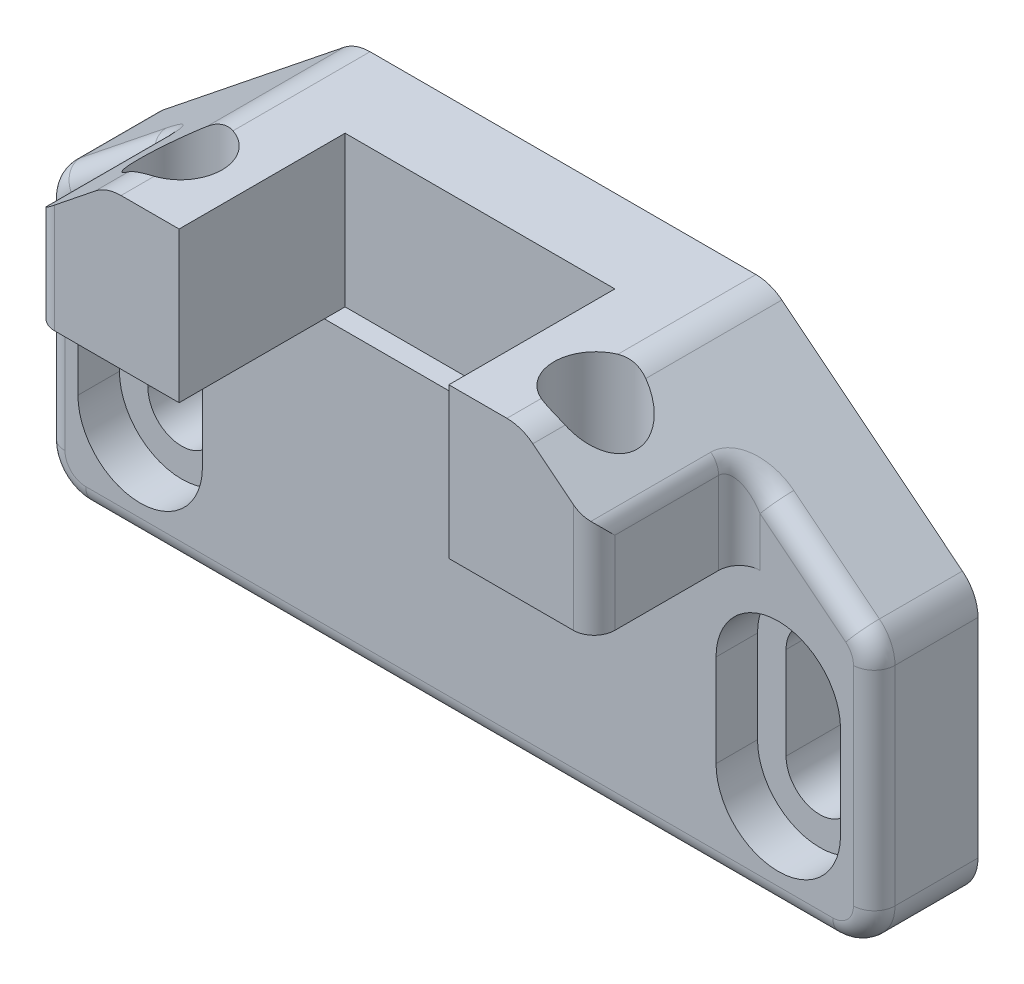
SolidWorks part; units mm, degrees
ref_plane "Front Plane" through (0, 0, 0) normal (0, 0, 1) x (1, 0, 0)
ref_plane "Top Plane" through (0, 0, 0) normal (0, 1, 0) x (1, 0, 0)
ref_plane "Right Plane" through (0, 0, 0) normal (1, 0, 0) x (0, 0, -1)
sketch "Sketch1" plane through (0, 0, 0) normal (0, 0, 1) x (1, 0, 0)
  line L0 (0, 0) -> (18, 0)
  line L1 (20, 2) -> (20, 12.0388)
  line L2 (19.2494, 13.6005) -> (10.5478, 20.5617)
  line L3 (9.2984, 21) -> (-9.2984, 21)
  line L4 (-10.5478, 20.5617) -> (-19.2494, 13.6005)
  line L5 (-20, 12.0388) -> (-20, 2)
  line L6 (-18, 0) -> (0, 0)
  line L7 (0, 21) -> (0, 0) construction
  line L8 (-15.375, 9.075) -> (-15.375, 4.625) construction
  line L9 (-13.75, 9.075) -> (-13.75, 4.625)
  line L10 (-17, 9.075) -> (-17, 4.625)
  line L11 (15.375, 9.075) -> (15.375, 4.625) construction
  line L12 (17, 9.075) -> (17, 4.625)
  line L13 (13.75, 9.075) -> (13.75, 4.625)
  arc A0 (-13.75, 9.075) -> (-17, 9.075) centre (-15.375, 9.075) ccw
  arc A1 (-17, 4.625) -> (-13.75, 4.625) centre (-15.375, 4.625) ccw
  arc A2 (17, 9.075) -> (13.75, 9.075) centre (15.375, 9.075) ccw
  arc A3 (13.75, 4.625) -> (17, 4.625) centre (15.375, 4.625) ccw
  arc A4 (-9.2984, 21) -> (-10.5478, 20.5617) centre (-9.2984, 19) ccw
  arc A5 (9.2984, 21) -> (10.5478, 20.5617) centre (9.2984, 19) cw
  arc A6 (-20, 12.0388) -> (-19.2494, 13.6005) centre (-18, 12.0388) cw
  arc A7 (19.2494, 13.6005) -> (20, 12.0388) centre (18, 12.0388) cw
  arc A8 (20, 2) -> (18, 0) centre (18, 2) cw
  arc A9 (-20, 2) -> (-18, 0) centre (-18, 2) ccw
  point P10 (-15.375, 6.85)
  point P16 (15.375, 6.85)
  point P23 (15.375, 3)
  point P24 (-15.375, 3)
  point P25 (-15.375, 10.7)
  point P28 (-10, 21)
  point P31 (10, 21)
  point P34 (-20, 13)
  point P37 (20, 13)
  point P40 (20, 0)
  point P43 (-20, 0)
  dimension "D14" = 2
  dimension "D1" = 20
  dimension "D2" = 20
  dimension "D3" = 21
  dimension "D4" = 13
  dimension "D5" = 13
  dimension "D6" = 20
  dimension "D7" = 3.25
  dimension "D8" = 3.25
  dimension "D9" = 3
  dimension "D10" = 3
  dimension "D11" = 7.7
  dimension "D12" = 3
  dimension "D13" = 3
extrude "Boss-Extrude1" add sketch "Sketch1" along normal blind 5
sketch "Sketch2" plane through (0, 0, 5) normal (0, 0, 1) x (1, 0, 0)
  line L0 (-15.375, 4.625) -> (-15.375, 9.075) construction
  line L1 (-18.375, 4.625) -> (-18.375, 9.075)
  line L2 (-12.375, 4.625) -> (-12.375, 9.075)
  line L3 (15.375, 4.625) -> (15.375, 9.075) construction
  line L4 (12.375, 4.625) -> (12.375, 9.075)
  line L5 (18.375, 4.625) -> (18.375, 9.075)
  arc A0 (-18.375, 4.625) -> (-12.375, 4.625) centre (-15.375, 4.625) ccw
  arc A1 (-12.375, 9.075) -> (-18.375, 9.075) centre (-15.375, 9.075) ccw
  arc A2 (12.375, 4.625) -> (18.375, 4.625) centre (15.375, 4.625) ccw
  arc A3 (18.375, 9.075) -> (12.375, 9.075) centre (15.375, 9.075) ccw
  point P4 (-15.375, 6.85)
  point P9 (15.375, 6.85)
  dimension "D1" = 6
  dimension "D2" = 6
extrude "Cut-Extrude1" cut sketch "Sketch2" against normal blind 2
sketch "Sketch3" plane through (0, 0, 5) normal (0, 0, 1) x (1, 0, 0)
  line L0 (-13.5, 13.75) -> (13.5, 13.75)
  line L1 (13.5, 13.75) -> (13.5, 21)
  line L2 (13.5, 21) -> (-13.5, 21)
  line L3 (-13.5, 21) -> (-13.5, 13.75)
  line L4 (0, 21) -> (0, 0) construction
  line L5 (9.2984, 21) -> (-9.2984, 21) construction
  point P6 (0, 0)
  dimension "D1" = 27
  dimension "D2" = 7.25
extrude "Boss-Extrude2" add sketch "Sketch3" along normal blind 7
sketch "Sketch4" plane through (0, 0, 12) normal (0, 0, 1) x (1, 0, 0)
  line L0 (13.5, 18.2) -> (10.5478, 20.5617)
  line L1 (-13.5, 18.2) -> (-10.5478, 20.5617)
  line L2 (13.5, 18.2) -> (13.5, 21)
  line L3 (13.5, 21) -> (9.2984, 21)
  line L4 (13.5, 21) -> (-13.5, 21) construction
  line L5 (-13.5, 18.2) -> (-13.5, 21)
  line L6 (-13.5, 21) -> (-9.2984, 21)
  line L7 (-6.5, 21) -> (-6.5, 13.75)
  line L8 (-13.5, 13.75) -> (13.5, 13.75) construction
  line L9 (-6.5, 13.75) -> (6.5, 13.75)
  line L10 (-13.5, 13.75) -> (13.5, 13.75) construction
  line L11 (6.5, 13.75) -> (6.5, 21)
  line L12 (6.5, 21) -> (-6.5, 21)
  line L13 (0, 21) -> (0, 0) construction
  arc A0 (-10.5478, 20.5617) -> (-9.2984, 21) centre (-9.2984, 19) cw
  arc A1 (-9.2984, 21) -> (-10.5478, 20.5617) centre (-9.2984, 19) ccw construction
  arc A2 (10.5478, 20.5617) -> (9.2984, 21) centre (9.2984, 19) ccw
  point P32 (0, 0)
  dimension "D1" = 13
extrude "Cut-Extrude2" cut sketch "Sketch4" against normal blind 8
sketch "Sketch5" plane through (0, 13.75, 0) normal (0, -1, 0) x (1, 0, 0)
  line L2 (-13.5, 12) -> (-6.5, 12) construction
  line L3 (6.5, 12) -> (13.5, 12) construction
  circle A0 centre (-9.9308, 8.5) radius 2
  circle A1 centre (10.0692, 8.5) radius 2
  point P7 (-9.6925, 9.1873)
  dimension "D1" = 4
  dimension "D3" = 3.5
  dimension "D4" = 3.5
  dimension "D2" = 20
extrude "Cut-Extrude3" cut sketch "Sketch5" against normal through all
fillet "Fillet1" radius 1 15 edges at (13.5, 18.2, 8.5) (16.3747, 15.9002, 5) (19.8026, 12.9051, 5) (20, 7.0194, 5) (19.4142, 0.5858, 5) (0, 0, 5) (-19.4142, 0.5858, 5) (-20, 7.0194, 5) (-19.8026, 12.9051, 5) (-16.3747, 15.9002, 5) (-13.5, 18.2, 8.5) (-13.5, 15.975, 5) (13.5, 15.975, 5) (13.5, 15.975, 12) (-13.5, 15.975, 12)
